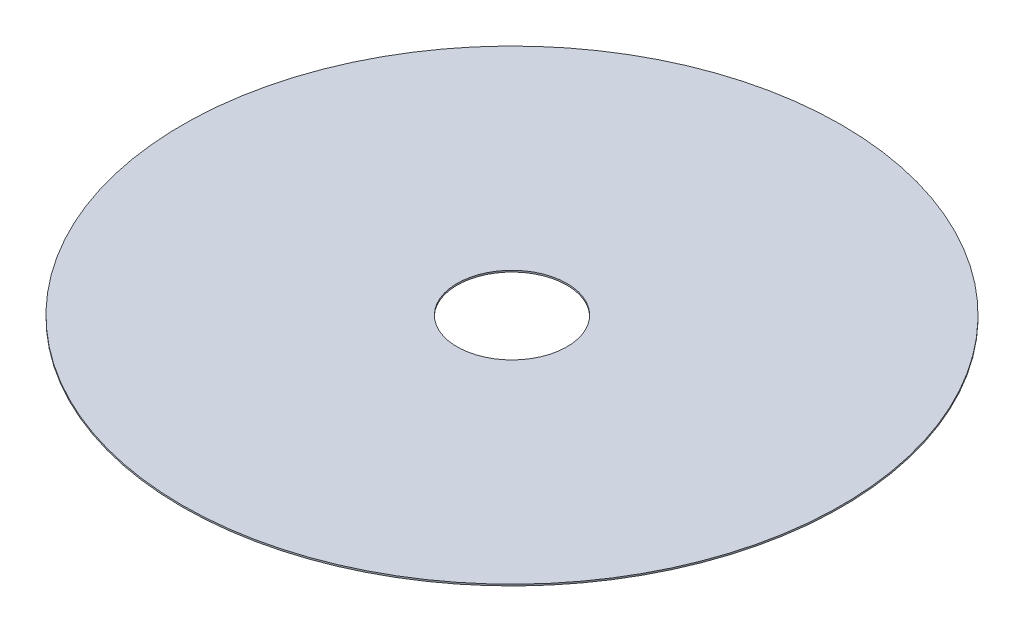
SolidWorks part; units mm, degrees
material "AISI 1020"
ref_plane "Front Plane" through (0, 0, 0) normal (0, 0, 1) x (1, 0, 0)
ref_plane "Top Plane" through (0, 0, 0) normal (0, 1, 0) x (1, 0, 0)
ref_plane "Right Plane" through (0, 0, 0) normal (1, 0, 0) x (0, 0, -1)
sketch "Sketch1" plane through (0, 0, 0) normal (0, 0, 1) x (1, 0, 0)
  line L0 (0, 0) -> (0, 30.5205) construction
  line L1 (0, 0) -> (250, 0)
  line L2 (250, 3.5) -> (250, -3.5)
  line L3 (250, 3.5) -> (1500, 3.5)
  line L4 (1500, 3.5) -> (1500, -3.5)
  line L5 (1500, -3.5) -> (250, -3.5)
  point P7 (250, 0)
revolve "Revolve1" add sketch "Sketch1" angle 360 about L0
sketch "Sketch2" plane through (0, 3.5, 0) normal (0, 1, 0) x (1, 0, 0)
  line L0 (0, -1460) -> (0, 1460)
  line L1 (-1460, 0) -> (1460, 0)
  circle A6 centre (0, 1460) radius 25
  circle A8 centre (-1460, 0) radius 25
  circle A9 centre (1460, 0) radius 25
  circle A10 centre (0, -1460) radius 25
  point P7 (0, 0)
  point P8 (0, 0)
